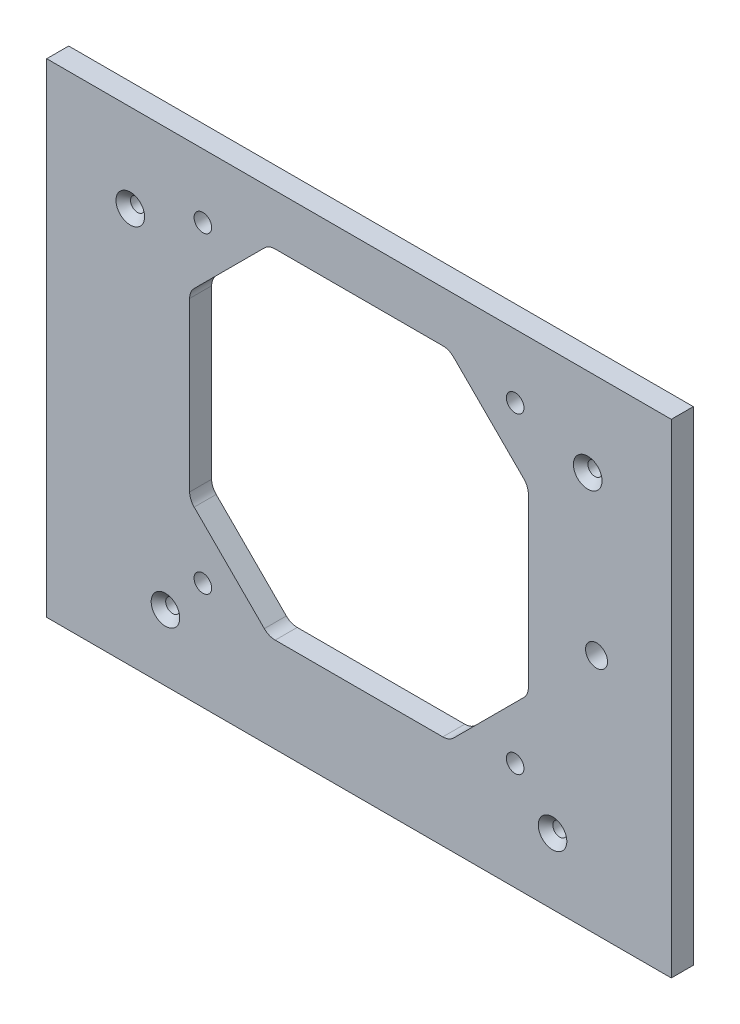
SolidWorks part; units mm, degrees
ref_plane "Front Plane" through (0, 0, 0) normal (0, 0, 1) x (1, 0, 0)
ref_plane "Top Plane" through (0, 0, 0) normal (0, 1, 0) x (1, 0, 0)
ref_plane "Right Plane" through (0, 0, 0) normal (1, 0, 0) x (0, 0, -1)
sketch "Sketch1" plane through (0, 0, 0) normal (0, 0, 1) x (1, 0, 0)
  line L1 (71, -55) -> (-71, -55)
  line L2 (71, -55) -> (71, 55)
  line L3 (71, 55) -> (-71, 55)
  line L4 (-71, -55) -> (-71, 55)
  line L5 (71, -55) -> (-71, 55) construction
  line L6 (71, 55) -> (-71, -55) construction
  point P0 (0, 0)
  dimension "D1" = 142
  dimension "D2" = 110
extrude "Boss-Extrude1" add sketch "Sketch1" along normal mid plane 5
sketch "Sketch7" plane through (0, 0, 2.5) normal (0, 0, 1) x (1, 0, 0)
  line L0 (-20.5, 43.5) -> (-38.5, 25.5)
  line L1 (20.5, -33.5) -> (-20.5, -33.5)
  line L2 (38.5, -15.5) -> (38.5, 25.5)
  line L3 (20.5, 43.5) -> (-20.5, 43.5)
  line L4 (-38.5, -15.5) -> (-38.5, 25.5)
  line L5 (38.5, -33.5) -> (-38.5, 43.5) construction
  line L6 (38.5, 43.5) -> (-38.5, -33.5) construction
  line L7 (-20.5, -33.5) -> (-38.5, -15.5)
  line L8 (38.5, -15.5) -> (20.5, -33.5)
  line L9 (38.5, 25.5) -> (20.5, 43.5)
  circle A0 centre (0, 5) radius 38.5 construction
  circle A1 centre (-35.5, -30.5) radius 2
  circle A2 centre (35.5, -30.5) radius 2
  circle A3 centre (35.5, 40.5) radius 2
  circle A4 centre (-35.5, 40.5) radius 2
  point P23 (0, 2.7023)
  point P24 (0, 0)
  point P25 (0, 4.5496)
  dimension "D3" = 4
  dimension "D10" = 77
  dimension "D2" = 5
  dimension "D4" = 71
  dimension "D5" = 71
  dimension "D11" = 77
extrude "Fan" cut sketch "Sketch7" against normal through all
chamfer "FanChamfer" [suppressed] distance 3 angle 45
sketch "Sketch8" plane through (0, 0, 2.5) normal (0, 0, 1) x (1, 0, 0)
  line L2 (71, -55) -> (71, 55) construction
  circle A0 centre (54, 0) radius 2.5
  dimension "D1" = 17
  dimension "D2" = 5
extrude "ForLED" cut sketch "Sketch8" against normal through all
fillet "Fillet1" radius 3.5 8 edges at (38.5, 25.5, 0) (38.5, -15.5, 0) (20.5, -33.5, 0) (-38.5, -15.5, 0) (-38.5, 25.5, 0) (-20.5, 43.5, 0) (20.5, 43.5, 0) (-20.5, -33.5, 0)
hole_wizard "Ø3.2 (3.2) Diameter Hole1" positions "Sketch9" profile "Sketch10" hole size "Ø3.2" standard "ANSI Metric" end condition through all
sketch "Sketch9" plane through (0, 0, 2.5) normal (0, 0, 1) x (1, 0, 0)
  line L0 (71, 55) -> (-71, 55) construction
  line L1 (-71, 55) -> (-71, -55) construction
  line L2 (71, -55) -> (71, 55) construction
  point P0 (-52, 35)
  point P2 (52, 35)
  point P5 (0, 0)
  dimension "D1" = 20
  dimension "D2" = 19
  dimension "D3" = 19
sketch "Sketch10" plane through (-52, 35, 2.5) normal (1, 0, 0) x (0, -1, 0)
  line L0 (0, 0) -> (0, 5)
  line L1 (0, 5) -> (1.6, 5)
  line L2 (1.6, 5) -> (1.6, 1.65)
  line L3 (1.6, 1.65) -> (3.25, 0)
  line L5 (3.25, 0) -> (0, 0)
  line L6 (-1.6, 1.65) -> (-3.25, 0) construction
  line L11 (0, -6.35) -> (0, 107.95) construction
  dimension "Thru Hole Dia." = 3.2
  dimension "Thru Hole Depth" = 5
  dimension "Near C'Sink Dia." = 6.5
  dimension "Near C'Sink Angle" = 90
hole_wizard "Ø3.2 (3.2) Diameter Hole2" positions "Sketch11" profile "Sketch12" hole size "Ø3.2" standard "ANSI Metric" end condition through all
sketch "Sketch11" plane through (0, 0, 2.5) normal (0, 0, 1) x (1, 0, 0)
  line L0 (-71, -55) -> (71, -55) construction
  line L1 (-71, 55) -> (-71, -55) construction
  line L2 (71, -55) -> (71, 55) construction
  point P0 (-44, -40)
  point P2 (44, -40)
  point P7 (0, 0)
  dimension "D1" = 15
  dimension "D2" = 27
  dimension "D3" = 27
sketch "Sketch12" plane through (-44, -40, 2.5) normal (1, 0, 0) x (0, -1, 0)
  line L0 (0, 0) -> (0, 5)
  line L1 (0, 5) -> (1.6, 5)
  line L2 (1.6, 5) -> (1.6, 1.65)
  line L3 (1.6, 1.65) -> (3.25, 0)
  line L5 (3.25, 0) -> (0, 0)
  line L6 (-1.6, 1.65) -> (-3.25, 0) construction
  line L11 (0, -6.35) -> (0, 107.95) construction
  dimension "Thru Hole Dia." = 3.2
  dimension "Thru Hole Depth" = 5
  dimension "Near C'Sink Dia." = 6.5
  dimension "Near C'Sink Angle" = 90
equation "\"D3@Sketch9\"=\"D2@Sketch9\""
equation "\"D3@Sketch11\"=\"D2@Sketch11\""
